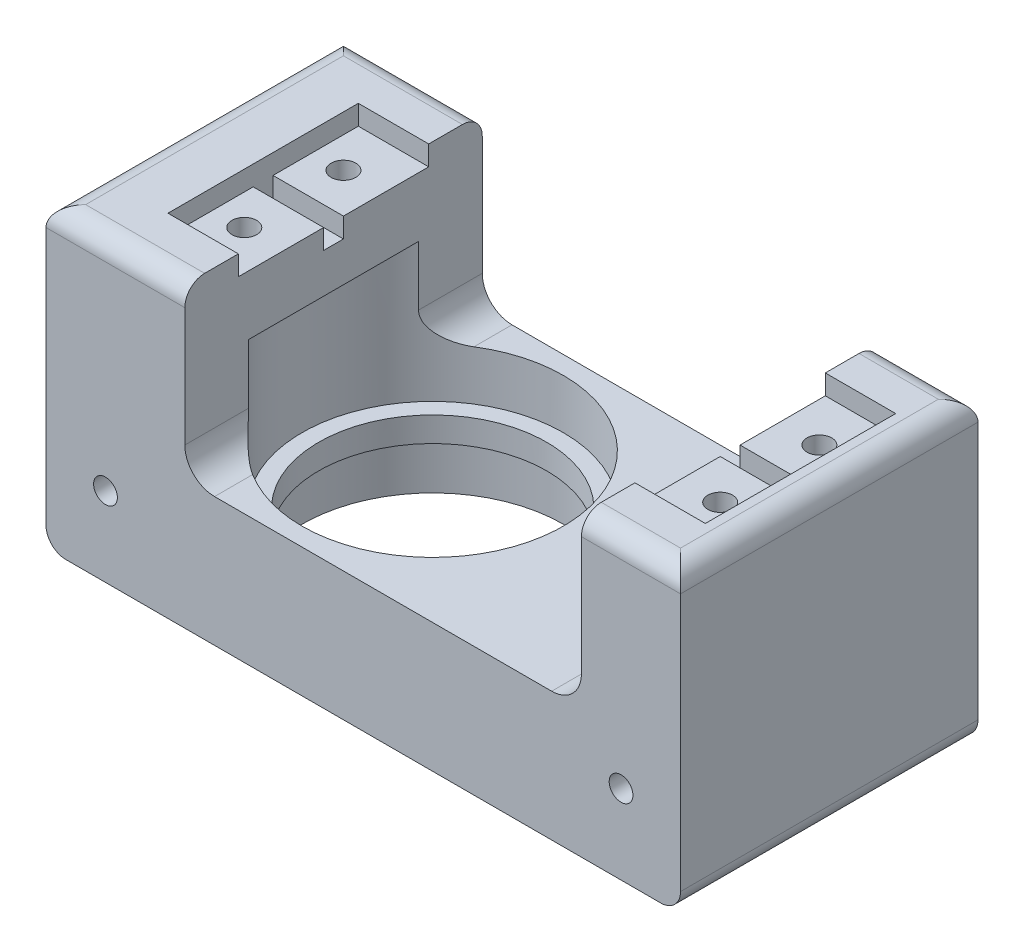
SolidWorks part; units mm, degrees
ref_plane "Спереди" through (0, 0, 0) normal (0, 0, 1) x (1, 0, 0)
ref_plane "Сверху" through (0, 0, 0) normal (0, 1, 0) x (1, 0, 0)
ref_plane "Справа" through (0, 0, 0) normal (1, 0, 0) x (0, 0, -1)
sketch "Эскиз1" plane through (0, 0, 0) normal (0, 1, 0) x (1, 0, 0)
  line L0 (0, 15) -> (0, -15) construction
  line L1 (-24, 15) -> (40, 15)
  line L2 (-24, 15) -> (-24, -15)
  line L3 (-24, -15) -> (40, -15)
  line L4 (40, 15) -> (40, -15)
  line L6 (-24, 0) -> (40, 0) construction
  point P6 (0, 0)
  dimension "D1" = 30
  dimension "D2" = 24
  dimension "D3" = 40
extrude "тело для подшипников" add sketch "Эскиз1" along normal blind 13
sketch "Эскиз2" plane through (0, 13, 0) normal (0, 1, 0) x (1, 0, 0)
  circle A0 centre (0, 0) radius 13.175
  dimension "D1" = 26.35
extrude "подшипник верхний" cut sketch "Эскиз2" against normal blind 5
sketch "Эскиз3" plane through (0, 0, 0) normal (0, -1, 0) x (1, 0, 0)
  circle A0 centre (0, 0) radius 13.175
  dimension "D1" = 26.35
extrude "подшипник нижний" cut sketch "Эскиз3" against normal blind 5.5
sketch "Эскиз4" plane through (0, 8, 0) normal (0, 1, 0) x (1, 0, 0)
  circle A0 centre (0, 0) radius 11.5
  dimension "D1" = 23
extrude "отверстие под ось" cut sketch "Эскиз4" against normal through all
sketch "Эскиз8" plane through (0, 13, 0) normal (0, 1, 0) x (1, 0, 0)
  line L0 (-24, 0) -> (40, 0) construction
  line L1 (-24, 15) -> (40, 15)
  line L2 (-24, 15) -> (-24, -15)
  line L3 (-24, -15) -> (40, -15)
  line L4 (40, 15) -> (40, -15)
  line L5 (-24, 15) -> (-24, -15) construction
  line L6 (0, 15) -> (0, -15) construction
  circle A0 centre (0, 0) radius 13.175
  circle A1 centre (0, 0) radius 13.175 construction
  dimension "D2" = 40
extrude "основание под сервой" add sketch "Эскиз8" along normal blind 3
sketch "Эскиз9" plane through (0, 16, 0) normal (0, 1, 0) x (1, 0, 0)
  line L0 (40, 15) -> (-24, 15) construction
  line L1 (-20, 15) -> (-10, 15)
  line L2 (-20, 15) -> (-20, -15)
  line L3 (-20, -15) -> (-10, -15)
  line L4 (-10, 15) -> (-10, 8.5779)
  line L5 (-24, -15) -> (40, -15) construction
  line L6 (0, 15) -> (0, -15) construction
  line L7 (40, 15) -> (30, 15)
  line L8 (40, 15) -> (40, -15)
  line L9 (40, -15) -> (30, -15)
  line L10 (30, 15) -> (30, -15)
  line L11 (-10, -8.5779) -> (-10, -15)
  line L12 (-24, 15) -> (-24, -15) construction
  arc A0 (-10, 8.5779) -> (-10, -8.5779) centre (0, 0) ccw
  circle A1 centre (0, 0) radius 13.175 construction
  dimension "D1" = 20
  dimension "D2" = 40
  dimension "D3" = 10
  dimension "D4" = 10
extrude "выступы к серве" add sketch "Эскиз9" along normal blind 12
sketch "Эскиз10" plane through (0, 28, 0) normal (0, 1, 0) x (1, 0, 0)
  line L0 (-20, 0) -> (40, 0) construction
  line L1 (-20, 15) -> (-20, -15) construction
  line L2 (40, -15) -> (40, 15) construction
  line L3 (-14, 5) -> (-14, -5) construction
  line L5 (34, 5) -> (34, -5) construction
  circle A0 centre (-14, 5) radius 1.25
  circle A1 centre (-14, -5) radius 1.25
  circle A2 centre (34, -5) radius 1.25
  circle A3 centre (34, 5) radius 1.25
  point P14 (34, 0)
  point P15 (-14, 0)
  dimension "D1" = 2.5
  dimension "D2" = 10
  dimension "D3" = 14
  dimension "D4" = 34
extrude "крепление сервы" cut sketch "Эскиз10" against normal blind 12
sketch "Эскиз11" plane through (0, 0, 15) normal (0, 0, 1) x (1, 0, 0)
  line L0 (-24, 8) -> (40, 8) construction
  line L1 (-24, 16) -> (-24, 0) construction
  line L2 (40, 28) -> (40, 0) construction
  line L4 (0, 16) -> (0, 0) construction
  line L5 (8, 0) -> (8, 16) construction
  line L6 (-10, 16) -> (30, 16) construction
  line L8 (-24, 0) -> (40, 0) construction
  circle A0 centre (-18, 8) radius 1.2
  circle A3 centre (34, 8) radius 1.2
  dimension "D1" = 2.4
  dimension "D2" = 52
extrude "Отверстия для шурупов" cut sketch "Эскиз11" against normal blind 11
mirror "Отверстия для шурупов с другой стороны" about plane through (0, 0, 0) normal (0, 0, 1) of "Отверстия для шурупов"
sketch "Эскиз12" plane through (0, 28, 0) normal (0, 1, 0) x (1, 0, 0)
  line L0 (-10, -15) -> (-10, -8.5779) construction
  line L1 (-10, 8.5779) -> (-10, 15) construction
  line L2 (-20, 15) -> (-10, 15)
  line L3 (-20, 15) -> (-20, 9.6)
  line L4 (-20, 9.6) -> (-10, 9.6)
  line L5 (-20, -15) -> (-10, -15)
  line L6 (-10, 15) -> (-10, 9.6)
  line L7 (-20, -15) -> (-20, -9.6)
  line L8 (-20, -9.6) -> (-10, -9.6)
  line L9 (-10, -15) -> (-10, -9.6)
  line L10 (30, 15) -> (30, -15) construction
  line L11 (40, -15) -> (30, -15)
  line L12 (40, -15) -> (40, -9.6)
  line L13 (40, -9.6) -> (30, -9.6)
  line L14 (30, -15) -> (30, -9.6)
  line L15 (40, 15) -> (30, 15) construction
  line L16 (40, 15) -> (30, 15)
  line L17 (40, 15) -> (40, 9.6)
  line L18 (40, 9.6) -> (30, 9.6)
  line L19 (30, 15) -> (30, 9.6)
  line L20 (40, -15) -> (40, 15) construction
  dimension "D1" = 5.4
extrude "бортики к серве" add sketch "Эскиз12" along normal blind 2
sketch "Эскиз14" plane through (0, 16, 0) normal (0, 1, 0) x (1, 0, 0)
  line L0 (-10, 15) -> (-10, 8.5779)
  line L1 (-10, 15) -> (30, 15)
  line L2 (30, 15) -> (30, -15)
  line L3 (30, -15) -> (-10, -15)
  line L4 (-10, -15) -> (-10, -8.5779)
  arc A0 (-10, -8.5779) -> (-10, 8.5779) centre (0, 0) ccw
  arc A1 (-10, -8.5779) -> (-10, 8.5779) centre (0, 0) ccw construction
extrude "углубление впресовать подшипник" cut sketch "Эскиз14" against normal blind 3
sketch "Эскиз15" plane through (0, 28, 0) normal (0, 1, 0) x (1, 0, 0)
  line L1 (-20, 9.6) -> (-10, 9.6)
  line L2 (-20, 9.6) -> (-20, -9.6)
  line L3 (-20, -9.6) -> (-10, -9.6)
  line L4 (-10, 9.6) -> (-10, -9.6)
  circle A0 centre (-14, 5) radius 1.25
  circle A1 centre (-14, -5) radius 1.25
  circle A2 centre (-14, 5) radius 1.25 construction
  circle A3 centre (-14, -5) radius 1.25 construction
extrude "наплыв для саморезов" add sketch "Эскиз15" against normal blind 9
chamfer "Фаска5" distance 3 angle 45 1 edges at (-10, 19, 0)
sketch "Эскиз17" plane through (0, 28, 0) normal (0, 1, 0) x (1, 0, 0)
  line L0 (-10, -9.6) -> (-20, -9.6) construction
  line L1 (-20, 9.6) -> (-17.1, 9.6)
  line L2 (-20, 9.6) -> (-20, -9.6)
  line L3 (-20, -9.6) -> (-17.1, -9.6)
  line L4 (-17.1, 9.6) -> (-17.1, -9.6)
  line L5 (40, -9.6) -> (30, -9.6) construction
  line L6 (40, 9.6) -> (37.1, 9.6)
  line L7 (40, 9.6) -> (40, -9.6)
  line L8 (40, -9.6) -> (37.1, -9.6)
  line L9 (37.1, 9.6) -> (37.1, -9.6)
  line L10 (-20, 9.6) -> (-10, 9.6) construction
  line L11 (-20, 15) -> (-20, -15) construction
  line L12 (-20, 9.6) -> (-20, -9.6) construction
  dimension "D1" = 2.9
  dimension "D2" = 2.9
extrude "бортики к серве спереди" add sketch "Эскиз17" along normal up to surface (2 mm away) up to face at (-15, 30, -12.3)
sketch "Эскиз16" plane through (0, 28, 0) normal (0, 1, 0) x (1, 0, 0)
  line L0 (-17.1, 0) -> (37.1, 0) construction
  line L3 (-10, -9.6) -> (-10, 9.6) construction
  line L4 (-10, 1) -> (-17.1, 1)
  line L5 (-10, 1) -> (-10, -1)
  line L6 (-10, -1) -> (-17.1, -1)
  line L7 (-17.1, 1) -> (-17.1, -1)
  line L8 (30, 9.6) -> (30, -9.6) construction
  line L9 (30, -1) -> (37.1, -1)
  line L10 (30, -1) -> (30, 1)
  line L11 (30, 1) -> (37.1, 1)
  line L12 (37.1, -1) -> (37.1, 1)
  line L13 (-17.1, -9.6) -> (-17.1, 9.6) construction
  line L14 (-17.1, -9.6) -> (-17.1, 9.6) construction
  line L15 (37.1, 9.6) -> (37.1, -9.6) construction
  point P12 (-10, 0)
  point P19 (30, 0)
  dimension "D1" = 2
extrude "пазы под ребра жесткости сервы" cut sketch "Эскиз16" against normal blind 2
sketch "Эскиз18" plane through (0, 16, 0) normal (0, 1, 0) x (1, 0, 0)
  line L0 (-20, -15) -> (-10, -15) construction
  line L1 (-24, 15) -> (-20, 15)
  line L2 (-24, 15) -> (-24, -15)
  line L3 (-24, -15) -> (-20, -15)
  line L4 (-20, 15) -> (-20, -15)
  line L5 (-20, 15) -> (-20, -15) construction
extrude "площадка под светодиод" add sketch "Эскиз18" along normal up to surface (14 mm away) up to face at (-14.275, 30, 0)
fillet "Скругление4" radius 3 3 edges at (30, 13, 0) (-10, 13, -11.789) (-10, 13, 11.789)
fillet "Скругление5" radius 2 8 edges at (-24, 0, 0) (40, 0, 0) (35, 30, 15) (40, 30, 0) (35, 30, -15) (-17, 30, 15) (-24, 30, 0) (-17, 30, -15)
